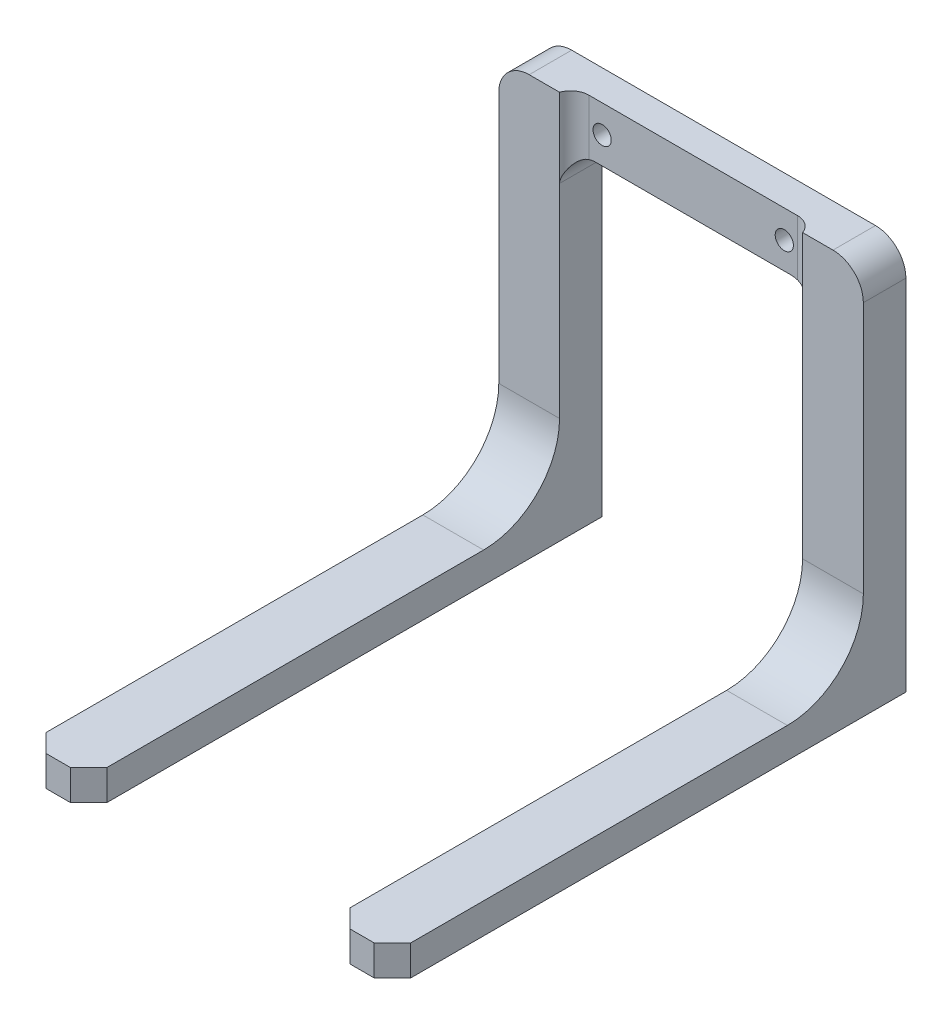
SolidWorks part; units mm, degrees
ref_plane "Front Plane" through (0, 0, 0) normal (0, 0, 1) x (1, 0, 0)
ref_plane "Top Plane" through (0, 0, 0) normal (0, 1, 0) x (1, 0, 0)
ref_plane "Right Plane" through (0, 0, 0) normal (1, 0, 0) x (0, 0, -1)
sketch "Sketch1" plane through (0, 0, 0) normal (0, 1, 0) x (1, 0, 0)
  line L1 (-30, 3.5) -> (30, 3.5)
  line L2 (-30, 3.5) -> (-30, -3.5)
  line L3 (-30, -3.5) -> (30, -3.5)
  line L4 (30, 3.5) -> (30, -3.5)
  line L5 (-30, 3.5) -> (30, -3.5) construction
  line L6 (-30, -3.5) -> (30, 3.5) construction
  point P0 (0, 0)
  dimension "D1" = 60
  dimension "D2" = 7
extrude "Boss-Extrude1" add sketch "Sketch1" along normal blind 9
sketch "Sketch2" plane through (0, 0, 3.5) normal (0, 0, 1) x (1, 0, 0)
  line L0 (-30, 9) -> (30, 9) construction
  line L1 (-20, 9) -> (20, 9)
  line L2 (-20, 9) -> (-20, 0)
  line L3 (-20, 0) -> (20, 0)
  line L4 (20, 9) -> (20, 0)
  line L5 (-30, 0) -> (30, 0) construction
  line L6 (-30, 9) -> (-30, 0) construction
  line L7 (30, 9) -> (30, 0) construction
  dimension "D1" = 10
  dimension "D2" = 10
extrude "Cut-Extrude1" cut sketch "Sketch2" against normal blind 2
fillet "Fillet2" radius 3 2 edges at (-20, 4.5, 1.5) (20, 4.5, 1.5)
fillet "Fillet3" radius 5 2 edges at (30, 9, 0) (-30, 9, 0)
sketch "Sketch3" plane through (0, 0, 0) normal (0, -1, 0) x (1, 0, 0)
  line L1 (-20, 3.5) -> (-30, 3.5)
  line L2 (-20, 3.5) -> (-20, -3.5)
  line L3 (-20, -3.5) -> (-30, -3.5)
  line L4 (-30, 3.5) -> (-30, -3.5)
  line L5 (20, 3.5) -> (30, 3.5)
  line L6 (20, 3.5) -> (20, -3.5)
  line L7 (20, -3.5) -> (30, -3.5)
  line L8 (30, 3.5) -> (30, -3.5)
extrude "Boss-Extrude2" add sketch "Sketch3" along normal blind 55
fillet "Fillet5" radius 4 2 edges at (20, 0, 0) (-20, 0, 0)
sketch "Sketch4" plane through (0, 0, 3.5) normal (0, 0, 1) x (1, 0, 0)
  line L0 (-20, -55) -> (-20, -4) construction
  line L1 (-30, -55) -> (-20, -55)
  line L2 (-30, -55) -> (-30, -50)
  line L3 (-30, -50) -> (-20, -50)
  line L4 (-20, -55) -> (-20, -50)
  dimension "D1" = 5
extrude "Boss-Extrude3" add sketch "Sketch4" along normal blind 77.5
sketch "Sketch5" plane through (0, 0, 3.5) normal (0, 0, 1) x (1, 0, 0)
  line L0 (30, 4) -> (30, -55) construction
  line L1 (20, -55) -> (30, -55)
  line L2 (20, -55) -> (20, -50)
  line L3 (20, -50) -> (30, -50)
  line L4 (30, -55) -> (30, -50)
  dimension "D1" = 5
extrude "Boss-Extrude4" add sketch "Sketch5" along normal blind 77.5
fillet "Fillet7" radius 12.5 2 edges at (25, -50, 3.5) (-25, -50, 3.5)
chamfer "Chamfer2" distance 3 angle 45 4 edges at (30, -52.5, 81) (20, -52.5, 81) (-20, -52.5, 81) (-30, -52.5, 81)
sketch "Sketch6" plane through (0, 0, -3.5) normal (0, 0, -1) x (-1, 0, 0)
  line L0 (-17.1716, -0.1754) -> (-30, -0.1754) construction
  line L1 (-30, 4) -> (-30, -55) construction
  line L2 (16, 0) -> (30, 0) construction
  line L3 (30, 4) -> (30, -55) construction
  line L4 (-30, 2.3246) -> (30, 2.3246) construction
  line L5 (-29.3301, 6.5) -> (29.3301, 6.5) construction
  line L6 (-25, 9) -> (25, 9) construction
  line L7 (0, 2.3246) -> (0, 6.5) construction
  line L8 (0, 4.4123) -> (29.983, 4.4123) construction
  line L9 (0, 4.4123) -> (-29.983, 4.4123) construction
  arc A0 (-25, 9) -> (-30, 4) centre (-25, 4) ccw construction
  arc A1 (30, 4) -> (25, 9) centre (25, 4) ccw construction
  circle A2 centre (-14.9915, 4.4123) radius 1.5
  circle A3 centre (14.9915, 4.4123) radius 1.5
  dimension "D1" = 2.5
  dimension "D2" = 2.5
extrude "Cut-Extrude2" cut sketch "Sketch6" against normal blind 10
